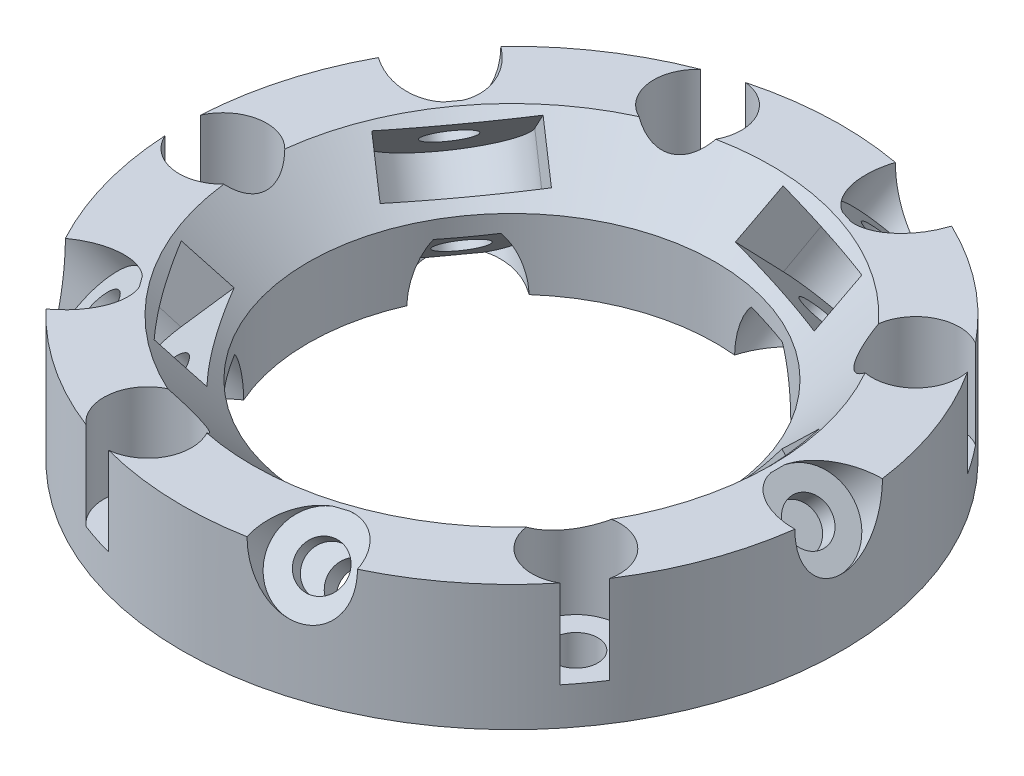
SolidWorks part; units mm, degrees
ref_plane "Front Plane" through (0, 0, 0) normal (0, 0, 1) x (1, 0, 0)
ref_plane "Top Plane" through (0, 0, 0) normal (0, 1, 0) x (1, 0, 0)
ref_plane "Right Plane" through (0, 0, 0) normal (1, 0, 0) x (0, 0, -1)
ref_axis "Axis1" through (0, 55, 0) along (0, -1, 0)
sketch "Sketch2" plane through (0, 0, 0) normal (0, 0, 1) x (1, 0, 0)
  line L0 (23.2574, 7.7041) -> (23.2574, 15.7041)
  line L1 (23.2574, 15.7041) -> (29.6213, 22.0681)
  line L2 (29.6213, 22.0681) -> (37.6213, 22.0681)
  line L3 (37.6213, 22.0681) -> (37.6213, 7.7041)
  line L4 (37.6213, 7.7041) -> (23.2574, 7.7041)
  line L5 (24.6716, 17.1184) -> (32.4497, 9.3402) construction
  line L6 (32.4497, 9.3402) -> (35.9853, 12.8757) construction
  line L7 (35.9853, 12.8757) -> (28.2071, 20.6539) construction
  line L8 (27.5, 14.2899) -> (31.0355, 17.8255) construction
  line L10 (0, 55) -> (0, -55) construction
  point P11 (0, 0)
  point P12 (0, 0)
  point P13 (0, 0)
  point P14 (0, 0)
  point P15 (68.1648, 19.7072)
  dimension "D1" = 11
  dimension "D2" = 5
  dimension "D3" = 7
  dimension "D4" = 2
  dimension "D5" = 45
  dimension "D6" = 2
  dimension "D7" = 8
  dimension "D8" = 8
  dimension "D9" = 27.5
ref_plane "Plane1" through (24.4305, 24.4305, 0) normal (0.7071, 0.7071, 0) x (0.7071, -0.7071, 0)
sketch "Sketch3" plane through (24.4305, 24.4305, 0) normal (0.7071, 0.7071, 0) x (0.7071, -0.7071, 0)
  line L0 (10.7803, -7) -> (3.7803, -7)
  line L2 (3.7803, 7) -> (10.7803, 7)
  line L3 (3.7803, 7) -> (3.7803, -7)
  circle A1 centre (10.7803, 0) radius 2.5
  arc A2 (10.7803, 7) -> (10.7803, -7) centre (10.7803, 0) cw
  point P0 (9.3409, 0)
  dimension "D1" = 5
revolve "Revolve1" add sketch "Sketch2" angle 360 about axis through (0, 55, 0) along (0, -1, 0)
extrude "Cut-Extrude1" cut sketch "Sketch3" against normal blind 5.5 and the other way blind 0.5
extrude "Cut-Extrude2" cut sketch "Sketch3<2>" against normal through all both and the other way through all contours A1
sketch "Sketch3<2>" plane through (24.4305, 24.4305, 0) normal (0.7071, 0.7071, 0) x (0.7071, -0.7071, 0) same geometry as "Sketch3"
sketch "Sketch5" plane through (20.5414, 20.5414, 0) normal (0.7071, 0.7071, 0) x (0, 0, -1)
  circle A0 centre (0, -10.7803) radius 5
  dimension "D1" = 10
extrude "Cut-Extrude3" cut sketch "Sketch5" against normal blind 5.5 from offset 3 offset against normal yes
extrude "Cut-Extrude4" cut sketch "Sketch5<2>" along normal blind 5.5 from offset 8
sketch "Sketch5<2>" plane through (20.5414, 20.5414, 0) normal (0.7071, 0.7071, 0) x (0, 0, -1) same geometry as "Sketch5"
pattern_circular "CirPattern1" count 5 over 360 about axis through (0, 55, 0) along (0, -1, 0) of "Cut-Extrude4", "Cut-Extrude3", "Cut-Extrude2", "Cut-Extrude1"
sketch "Sketch6" plane through (0, 0, 0) normal (0, 1, 0) x (1, 0, 0)
  circle A0 centre (-33, 0) radius 2.5
  dimension "D1" = 5
  dimension "D2" = 33
extrude "Cut-Extrude5" cut sketch "Sketch6" along normal blind 30.2
sketch "Sketch7" plane through (0, 0, 0) normal (0, 1, 0) x (1, 0, 0)
  circle A0 centre (-33, 0) radius 5
  dimension "D1" = 10
extrude "Cut-Extrude6" cut sketch "Sketch7" along normal through all from offset 12
pattern_circular "CirPattern2" count 5 over 360 about axis through (0, 55, 0) along (0, -1, 0) of "Cut-Extrude6", "Cut-Extrude5"
